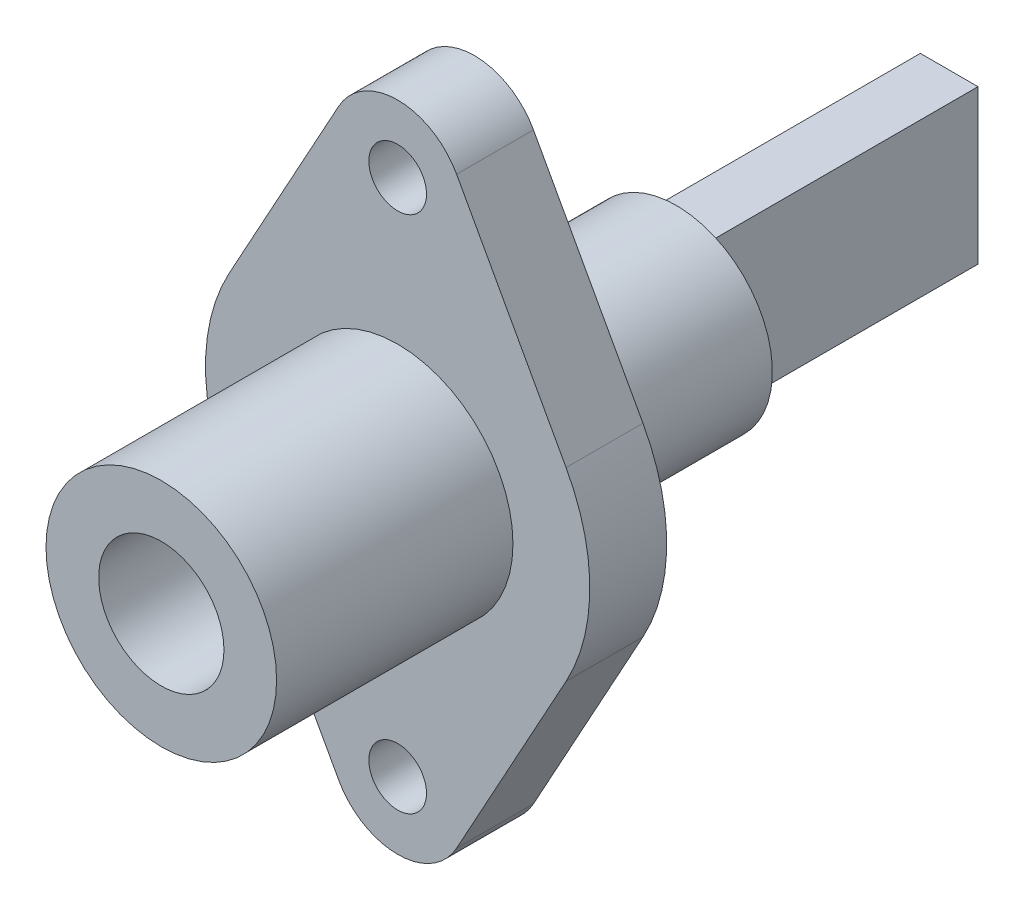
SolidWorks part; units mm, degrees
material "Custom Plastic"
ref_plane "X-Y Datum" through (0, 0, 0) normal (0, 0, 1) x (1, 0, 0)
ref_plane "X-Z Datum" through (0, 0, 0) normal (0, 1, 0) x (1, 0, 0)
ref_plane "Y-Z Datum" through (0, 0, 0) normal (1, 0, 0) x (0, 0, -1)
sketch "Sketch1" plane through (0, 0, 0) normal (0, 0, 1) x (1, 0, 0)
  line L0 (0, 17) -> (0, -17) construction
  line L1 (-10, 0) -> (10, 0) construction
  line L2 (-3.0676, 15.1852) -> (-8.7646, 4.8148)
  line L3 (3.0676, 15.1852) -> (8.7646, 4.8148)
  line L4 (3.0676, -15.1852) -> (8.7646, -4.8148)
  line L5 (-3.0676, -15.1852) -> (-8.7646, -4.8148)
  circle A0 centre (0, 0) radius 10
  circle A3 centre (0, 13.5) radius 3.5
  circle A4 centre (0, -13.5) radius 3.5
  circle A5 centre (0, 13.5) radius 1.5
  circle A6 centre (0, -13.5) radius 1.5
  point P4 (0, 0)
  point P8 (0, 0)
  dimension "D3" = 3
  dimension "D1" = 34
  dimension "D2" = 20
extrude "Boss-Extrude1" add sketch "Sketch1" along normal blind 4 contours A4 A6 | A0 A4 L4 | A0 | A3 A0 L3 | A3 A5 | A3 L2 A0 | L5 A4 A0 region at (-4.4007, 10.2822, 0) region at (0, 16.901, 0) region at (0, 0, 0) region at (4.4007, 10.2822, 0) region at (-4.4007, -10.2822, 0) region at (-2.9271, -11.7683, 0) region at (4.4007, -10.2822, 0)
sketch "Sketch2" plane through (0, 0, 4) normal (0, 0, 1) x (1, 0, 0)
  circle A0 centre (0, 0) radius 6
  dimension "D1" = 12
extrude "Boss-Extrude2" add sketch "Sketch2" along normal blind 12.3
sketch "Sketch3" plane through (0, 0, 0) normal (0, 0, -1) x (-1, 0, 0)
  circle A0 centre (0, 0) radius 7.5
  dimension "D1" = 15
extrude "Boss-Extrude3" add sketch "Sketch3" along normal blind 0.5
sketch "Sketch4" plane through (0, 0, -0.5) normal (0, 0, -1) x (-1, 0, 0)
  line L1 (-1.5, 4) -> (1.5, 4)
  line L2 (-1.5, 4) -> (-1.5, -4)
  line L3 (-1.5, -4) -> (1.5, -4)
  line L4 (1.5, 4) -> (1.5, -4)
  line L5 (-1.5, 4) -> (1.5, -4) construction
  line L6 (-1.5, -4) -> (1.5, 4) construction
  point P0 (0, 0)
  dimension "D1" = 8
  dimension "D2" = 3
extrude "Boss-Extrude4" add sketch "Sketch4" along normal blind 24.2
sketch "Sketch5" plane through (0, 0, -0.5) normal (0, 0, -1) x (-1, 0, 0)
  circle A0 centre (0, 0) radius 5
  dimension "D1" = 10
extrude "Boss-Extrude5" add sketch "Sketch5" along normal blind 10
sketch "Sketch6" plane through (0, 0, 16.3) normal (0, 0, 1) x (1, 0, 0)
  circle A0 centre (0, 0) radius 3.26
extrude "Cut-Extrude1" cut sketch "Sketch6" against normal blind 10
